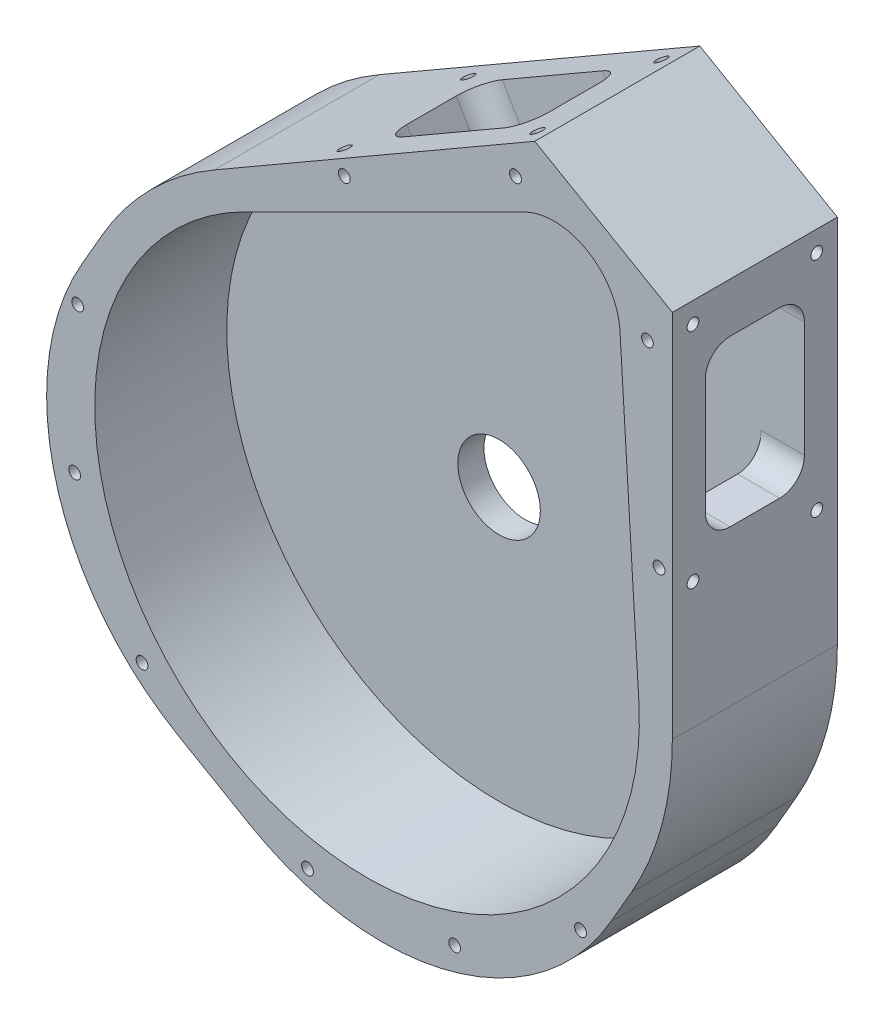
SolidWorks part; units mm, degrees
material "6061 Alloy"
ref_plane "Front Plane" through (0, 0, 0) normal (0, 0, 1) x (1, 0, 0)
ref_plane "Top Plane" through (0, 0, 0) normal (0, 1, 0) x (1, 0, 0)
ref_plane "Right Plane" through (0, 0, 0) normal (1, 0, 0) x (0, 0, -1)
sketch "Sketch1"
  line L0 (-73.3817, 0) -> (87.2477, 0) construction
  line L1 (-41.9015, -72.5756) -> (73.9359, 128.0608) construction
  line L2 (58.7375, 0) -> (58.7375, 101.7363) construction
  line L3 (58.7375, 101.7363) -> (-29.3687, 50.8682) construction
  line L4 (18.1523, 85.445) -> (65.1899, 58.2878) construction
  line L5 (26.1049, 90.019) -> (66.8523, 66.4934) construction
  line L6 (58.7375, 0) -> (58.7375, 71.1785)
  line L7 (32.2737, 86.4574) -> (58.7375, 71.1785)
  line L8 (32.2737, 86.4574) -> (-29.3687, 50.8682)
  line L9 (-105.9419, -6.6586) -> (53.9719, -98.9849) construction
  line L10 (-80.2369, -21.4994) -> (-50.8682, 29.3688)
  line L11 (21.4994, -80.2369) -> (50.8682, -29.3687)
  line L12 (-80.2369, -21.4994) -> (21.4994, -80.2369)
  circle A0 centre (0, 0) radius 58.7375 construction
  circle A1 centre (36.7743, 63.695) radius 9.525 construction
  circle A2 centre (36.7743, 47.82) radius 6.35 construction
  circle A3 centre (0, 0) radius 50.8 construction
  arc A4 (-50.8682, 29.3688) -> (-29.3687, 50.8682) centre (0, 0) cw
  arc A6 (50.8682, -29.3687) -> (58.7375, 0) centre (0, 0) ccw
  dimension "D1" = 117.475
  dimension "D3" = 19.05
  dimension "D4" = 12.7
  dimension "D5" = 60.325
  dimension "D6" = 101.6
  dimension "D2" = 60
  dimension "D7" = 7.9375
extrude "Boss-Extrude1" add sketch "Sketch1" along normal blind 31.75
ref_plane "Plane1" through (45.5056, 78.818, 31.75) normal (-0.866, 0.5, 0) x (0, 0, 1)
sketch "Sketch4" plane through (0, 0, 31.75) normal (0, 0, 1) x (1, 0, 0)
  line L2 (55.6492, 96.3872) -> (35.362, 61.2488) construction
  line L3 (58.7375, 71.1785) -> (32.2737, 86.4574) construction
  line L4 (52.2998, 3.0299) -> (-40.5836, 56.6561) construction
  line L5 (30.5684, 73.8129) -> (48.6397, 63.3794) construction
  line L6 (30.5684, 73.8129) -> (-23.526, 46.8079)
  line L7 (48.6397, 63.3794) -> (52.2998, 3.0299)
  circle A0 centre (0, 0) radius 52.3875 construction
  circle A1 centre (35.9806, 62.3202) radius 12.7 construction
  arc A2 (30.5684, 73.8129) -> (48.6397, 63.3794) centre (35.9806, 62.3202) cw
  arc A3 (52.2998, 3.0299) -> (-23.526, 46.8079) centre (0, 0) cw
  dimension "D1" = 104.775
  dimension "D2" = 19.05
  dimension "D3" = 25.4
extrude "Cut-Extrude3" cut sketch "Sketch4" against normal offset from surface (25.4 mm away) 6.35 up to face at (7.7701, 13.4581, 0)
sketch "Sketch5" plane through (58.7375, 0, 0) normal (1, 0, 0) x (0, 0, -1)
  line L0 (0, 0) -> (0, 71.1785) construction
  line L1 (-20.6375, 29.9035) -> (-11.1125, 29.9035)
  line L2 (-25.4, 34.666) -> (-25.4, 56.891)
  line L3 (-20.6375, 61.6535) -> (-11.1125, 61.6535)
  line L4 (-6.35, 34.666) -> (-6.35, 56.891)
  line L5 (-25.4, 29.9035) -> (-6.35, 61.6535) construction
  line L6 (-25.4, 61.6535) -> (-6.35, 29.9035) construction
  line L7 (-31.75, 71.1785) -> (0, 71.1785) construction
  arc A0 (-20.6375, 29.9035) -> (-25.4, 34.666) centre (-20.6375, 34.666) cw
  arc A1 (-11.1125, 29.9035) -> (-6.35, 34.666) centre (-11.1125, 34.666) ccw
  arc A2 (-11.1125, 61.6535) -> (-6.35, 56.891) centre (-11.1125, 56.891) cw
  arc A3 (-25.4, 56.891) -> (-20.6375, 61.6535) centre (-20.6375, 56.891) cw
  point P0 (-15.875, 45.7785)
  point P9 (-15.875, 71.1785)
  dimension "D4" = 4.7625
  dimension "D1" = 6.35
  dimension "D2" = 9.525
  dimension "D3" = 31.75
extrude "Cut-Extrude4" cut sketch "Sketch5" against normal up to surface (41.4727 mm away) up to plane "Plane1"
hole_wizard "#4-40 Tapped Hole1" positions "Sketch12" profile "Sketch11" tap size "#4-40" standard "Ansi Inch"
sketch "Sketch12" plane through (58.7375, 0, 0) normal (1, 0, 0) x (0, 0, -1)
  point P24 (-27.7813, 24.3473)
  point P27 (-3.9688, 24.3473)
  point P30 (-3.9688, 67.2098)
  point P33 (-27.7813, 67.2098)
sketch "Sketch11" plane through (58.7375, 24.3473, 27.7813) normal (0, 1, 0) x (0, 0, -1)
  line L0 (0, 0) -> (0, 5.7592)
  line L1 (0, 5.7592) -> (1.1303, 5.08)
  line L2 (1.1303, 5.08) -> (1.1303, 0)
  line L5 (1.1303, 0) -> (0, 0)
  line L10 (0, 5.7592) -> (-1.1303, 5.08) construction
  line L11 (0, -6.35) -> (0, 107.95) construction
  dimension "Tap Drill Dia." = 2.2606
  dimension "Tap Drill Depth" = 5.08
  dimension "Drill Angle" = 118
mirror "Mirror1" about plane through (45.5056, 78.818, 31.75) normal (-0.866, 0.5, 0) of "#4-40 Tapped Hole1", "Cut-Extrude4"
sketch "Sketch18"
  line L0 (53.4662, 3.099) -> (49.8051, 63.4632)
  line L1 (30.0582, 74.8641) -> (-24.0493, 47.8526)
  line L2 (52.2998, 3.0299) -> (48.6397, 63.3794)
  line L3 (30.5684, 73.8129) -> (-23.526, 46.8079)
  line L4 (52.2998, 3.0299) -> (48.6397, 63.3794) construction
  line L5 (30.5684, 73.8129) -> (-23.526, 46.8079) construction
  line L6 (55.6721, 3.2299) -> (52.0095, 63.6203)
  line L7 (29.0921, 76.8517) -> (-25.0389, 49.8284)
  arc A0 (-24.0493, 47.8526) -> (53.4662, 3.099) centre (0, 0) ccw
  arc A1 (49.8051, 63.4632) -> (30.0582, 74.8641) centre (35.9806, 62.3202) ccw
  arc A2 (48.6397, 63.3794) -> (30.5684, 73.8129) centre (35.9806, 62.3202) ccw
  arc A3 (-23.526, 46.8079) -> (52.2998, 3.0299) centre (0, 0) ccw
  arc A4 (48.6397, 63.3794) -> (30.5684, 73.8129) centre (35.9806, 62.3202) ccw construction
  arc A5 (-23.526, 46.8079) -> (52.2998, 3.0299) centre (0, 0) ccw construction
  arc A6 (-25.0389, 49.8284) -> (55.6721, 3.2299) centre (0, 0) ccw
  arc A7 (52.0095, 63.6203) -> (29.0921, 76.8517) centre (35.9806, 62.3202) ccw
  dimension "D1" = 0
  dimension "D2" = 1.1684
  dimension "D3" = 2.2098
hole_wizard "#4-40 Tapped Hole3" positions "Sketch22" profile "Sketch21" tap size "#4-40" standard "Ansi Inch"
sketch "Sketch22" plane through (0, 0, 31.75) normal (0, 0, 1) x (1, 0, 0)
  line L8 (57.6371, 3.3465) -> (53.9732, 63.7589)
  line L9 (28.2302, 78.6216) -> (-25.9204, 51.5885)
  line L10 (57.6371, 3.3465) -> (53.9732, 63.7589)
  line L11 (28.2302, 78.6216) -> (-25.9204, 51.5885)
  circle A0 centre (28.564, 78.7761) radius 2.3495
  circle A2 centre (-55.6745, 15.2835) radius 2.3495
  circle A3 centre (-56.2504, -13.0051) radius 2.3495
  circle A4 centre (-4.3756, 62.3441) radius 2.3495
  arc A16 (-25.9204, 51.5885) -> (57.6371, 3.3465) centre (0, 0) ccw
  arc A17 (53.9732, 63.7589) -> (28.2302, 78.6216) centre (35.9806, 62.3202) ccw
  arc A18 (-25.9204, 51.5885) -> (57.6371, 3.3465) centre (0, 0) ccw
  arc A19 (53.9732, 63.7589) -> (28.2302, 78.6216) centre (35.9806, 62.3202) ccw
  circle A20 centre (-56.2504, -13.0051) radius 1.4732
  circle A24 centre (-55.6745, 15.2835) radius 1.4732
  circle A25 centre (-43.2822, -38.2086) radius 1.4732
  circle A26 centre (-43.2822, -38.2086) radius 2.3495
  point P0 (28.564, 78.7761)
  point P3 (-55.6745, 15.2835)
  point P5 (-56.2504, -13.0051)
  point P23 (-4.3756, 62.3441)
  point P108 (-43.2822, -38.2086)
  dimension "D1" = 4.699
  dimension "D3" = 4.699
  dimension "D4" = 4.699
  dimension "D5" = 4.699
  dimension "D7" = 2.9464
  dimension "D8" = 2.9464
  dimension "D9" = 2.9464
  dimension "D10" = 4.699
  dimension "D6" = 1.9685
sketch "Sketch21" plane through (28.564, 78.7761, 31.75) normal (1, 0, 0) x (0, -1, 0)
  line L0 (0, 0) -> (0, 9.5692)
  line L1 (0, 9.5692) -> (1.1303, 8.89)
  line L2 (1.1303, 8.89) -> (1.1303, 0)
  line L5 (1.1303, 0) -> (0, 0)
  line L10 (0, 9.5692) -> (-1.1303, 8.89) construction
  line L11 (0, -6.35) -> (0, 107.95) construction
  dimension "Tap Drill Dia." = 2.2606
  dimension "Tap Drill Depth" = 8.89
  dimension "Drill Angle" = 118
mirror "Mirror2" about plane through (45.5056, 78.818, 31.75) normal (-0.866, 0.5, 0) of "#4-40 Tapped Hole3"
sketch "Sketch23" plane through (0, 0, 0) normal (0, 0, -1) x (-1, 0, 0)
  circle A0 centre (0, 0) radius 7.9375
  circle A1 centre (-35.8185, 62.0395) radius 7.9375
  dimension "D1" = 15.875
extrude "Cut-Extrude6" cut sketch "Sketch23" against normal through all
sketch "Sketch24" plane through (0, 0, 0) normal (0, 0, -1) x (-1, 0, 0)
  circle A0 centre (0, 0) radius 10.0076
  circle A1 centre (-35.8185, 62.0395) radius 10.0076
  dimension "D1" = 20.0152
extrude "Cut-Extrude9" cut sketch "Sketch24" against normal blind 1.3208
hole_wizard "#4-40 Tapped Hole4" positions "Sketch27" profile "Sketch26" tap size "#4-40" standard "Ansi Inch"
sketch "Sketch27" plane through (0, 0, 6.35) normal (0, 0, 1) x (1, 0, 0)
  point P1 (35.8185, 46.0375)
sketch "Sketch26" plane through (35.8185, 46.0375, 6.35) normal (1, 0, 0) x (0, -1, 0)
  line L0 (0, 0) -> (0, 4.9972)
  line L1 (0, 4.9972) -> (1.1303, 4.318)
  line L2 (1.1303, 4.318) -> (1.1303, 0)
  line L5 (1.1303, 0) -> (0, 0)
  line L10 (0, 4.9972) -> (-1.1303, 4.318) construction
  line L11 (0, -6.35) -> (0, 107.95) construction
  dimension "Tap Drill Dia." = 2.2606
  dimension "Tap Drill Depth" = 4.318
  dimension "Drill Angle" = 118
mirror "Mirror3" about plane through (45.5056, 78.818, 31.75) normal (-0.866, 0.5, 0) of "#4-40 Tapped Hole4"
hole_wizard "#2-56 Tapped Hole1" positions "Sketch29" profile "Sketch28" tap size "#2-56" standard "Ansi Inch"
sketch "Sketch29" plane through (0, 0, 0) normal (0, 0, -1) x (-1, 0, 0)
  point P1 (-51.69, 66.2923)
  point P4 (-31.5658, 77.911)
  point P7 (-19.947, 57.7867)
  point P10 (-40.0713, 46.168)
sketch "Sketch28" plane through (51.69, 66.2923, 0) normal (1, 0, 0) x (0, 1, 0)
  line L0 (0, 0) -> (0, 4.3442)
  line L1 (0, 4.3442) -> (0.889, 3.81)
  line L2 (0.889, 3.81) -> (0.889, 0)
  line L5 (0.889, 0) -> (0, 0)
  line L10 (0, 4.3442) -> (-0.889, 3.81) construction
  line L11 (0, -6.35) -> (0, 107.95) construction
  dimension "Tap Drill Dia." = 1.778
  dimension "Tap Drill Depth" = 3.81
  dimension "Drill Angle" = 118
pattern_linear "LPattern1" count 2 spacing 71.501 along (-0.5, -0.866, 0) of "#2-56 Tapped Hole1"
hole_wizard "#4-40 Tapped Hole5" positions "Sketch32" profile "Sketch31" tap size "#4-40" standard "Ansi Inch"
sketch "Sketch32" plane through (0, 0, 0) normal (0, 0, -1) x (-1, 0, 0)
  line L0 (64.0053, 36.9535) -> (-64.6452, -37.3229) construction
  line L3 (35.8992, 48.9457) -> (64.3331, -0.3033) construction
  line L6 (-35.362, 61.2488) -> (-55.6492, 96.3872) construction
  line L7 (50.8682, 29.3688) -> (80.2369, -21.4994) construction
  line L8 (-58.7375, 71.1785) -> (-32.2737, 86.4574) construction
  point P0 (44.9435, 33.2805)
  point P18 (51.2935, 22.282)
  point P24 (-38.4188, 79.2434)
  dimension "D1" = 6.35
  dimension "D2" = 6.35
  dimension "D3" = 3.175
  dimension "D4" = 6.35
  dimension "D5" = 3.175
sketch "Sketch31" plane through (-44.9435, 33.2805, 0) normal (1, 0, 0) x (0, 1, 0)
  line L0 (0, 0) -> (0, 9.5692)
  line L1 (0, 9.5692) -> (1.1303, 8.89)
  line L2 (1.1303, 8.89) -> (1.1303, 0)
  line L5 (1.1303, 0) -> (0, 0)
  line L10 (0, 9.5692) -> (-1.1303, 8.89) construction
  line L11 (0, -6.35) -> (0, 107.95) construction
  dimension "Tap Drill Dia." = 2.2606
  dimension "Tap Drill Depth" = 8.89
  dimension "Drill Angle" = 118
mirror "Mirror4" about plane through (45.5056, 78.818, 31.75) normal (-0.866, 0.5, 0) of "#4-40 Tapped Hole5"
fillet "Fillet3" radius 50.8 2 edges at (21.4994, -80.2369, 15.875) (-80.2369, -21.4994, 15.875)
ref_plane "Plane2" through (-29.3687, -50.8682, 0) normal (-0.5, -0.866, 0) x (0.866, -0.5, 0)
ref_plane "Plane4" through (50.8682, -29.3687, 0) normal (0.866, -0.5, 0) x (0, 0, -1)
sketch3d "3DSketch1"
  point P1 (21.4994, -80.2369, 0)
  point P2 (21.4994, -80.2369, 31.75)
